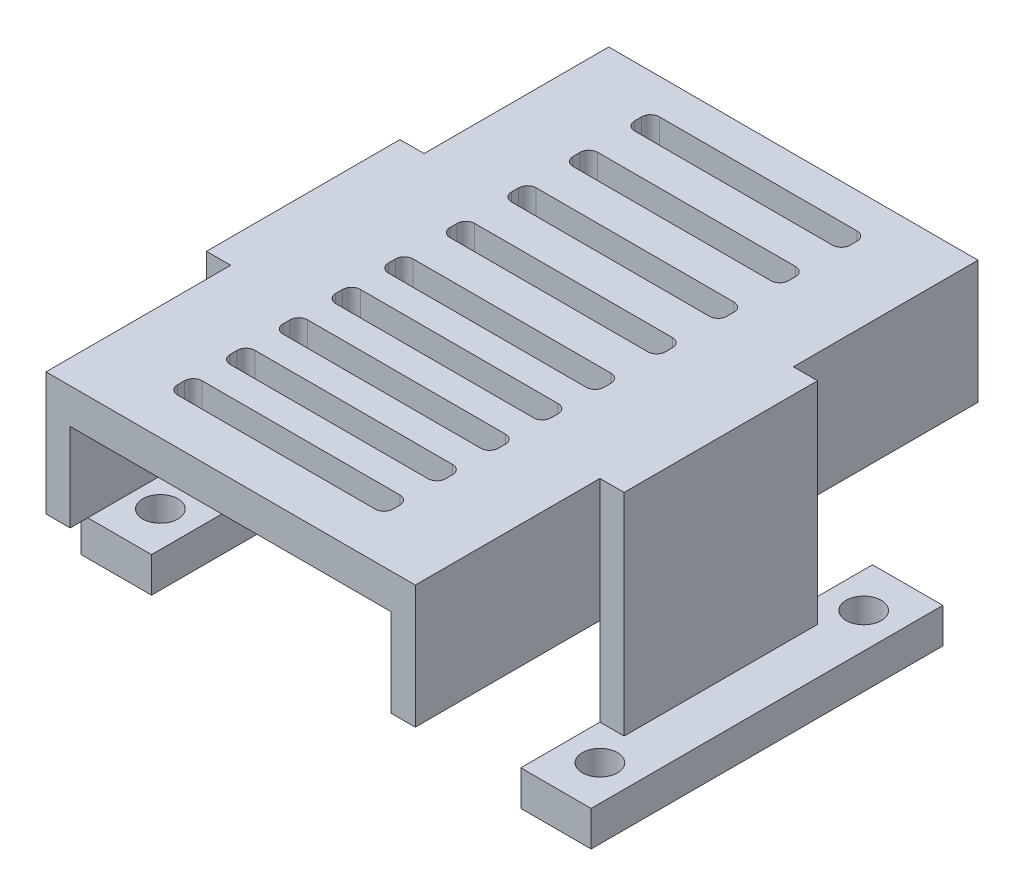
SolidWorks part; units mm, degrees
ref_plane "Front Plane" through (0, 0, 0) normal (0, 0, 1) x (1, 0, 0)
ref_plane "Top Plane" through (0, 0, 0) normal (0, 1, 0) x (1, 0, 0)
ref_plane "Right Plane" through (0, 0, 0) normal (1, 0, 0) x (0, 0, -1)
sketch "Sketch1" plane through (0, 0, 0) normal (0, 0, 1) x (1, 0, 0)
  line L0 (0, -55) -> (0, 55) construction
  line L7 (-23.75, 32) -> (23.75, 32)
  line L8 (-18.25, 28) -> (18.25, 28)
  line L9 (-21.5361, 18) -> (-21, 18) construction
  line L13 (-23.75, 32) -> (-23.75, 8)
  line L17 (21.5361, 18) -> (21, 18) construction
  line L19 (-21, 4) -> (-21, 18)
  line L22 (23.75, 32) -> (23.75, 8)
  line L25 (21, 4) -> (21, 18)
  line L27 (-29, 4) -> (-29, 8)
  line L28 (-29, 8) -> (-23.75, 8)
  line L29 (29, 8) -> (23.75, 8)
  line L30 (29, 4) -> (29, 8)
  line L31 (21, 4) -> (29, 4)
  line L32 (-18.25, 28) -> (-18.25, 18)
  line L33 (-29, 4) -> (-21, 4)
  line L34 (-18.25, 18) -> (-21, 18)
  line L35 (18.25, 28) -> (18.25, 18)
  line L36 (18.25, 18) -> (21, 18)
  dimension "D5" = 8
  dimension "D1" = 10
  dimension "D2" = 4
  dimension "D3" = 14
  dimension "D4" = 2.75
  dimension "D6" = 4
extrude "Boss-Extrude1" add sketch "Sketch1" along normal mid plane 64
sketch "Sketch8" plane through (0, 32, 0) normal (0, 1, 0) x (1, 0, 0)
  line L0 (12.25, 0) -> (-12.25, 0) construction
  line L1 (-12.25, 22.2) -> (12.25, 22.2) construction
  line L2 (-12.25, 22.2) -> (-12.25, -18.3) construction
  line L3 (-12.25, -18.3) -> (12.25, -18.3) construction
  line L4 (12.25, 22.2) -> (12.25, -18.3) construction
  line L5 (12.25, -2.8) -> (-12.25, -2.8) construction
  line L7 (11.25, -2.8) -> (-11.25, -2.8)
  line L8 (12.25, -1.8) -> (12.25, -1)
  line L9 (11.25, 0) -> (-11.25, 0)
  line L10 (-12.25, -1.8) -> (-12.25, -1)
  arc A0 (12.25, -1.8) -> (11.25, -2.8) centre (11.25, -1.8) cw
  arc A1 (12.25, -1) -> (11.25, 0) centre (11.25, -1) ccw
  arc A2 (-12.25, -1.8) -> (-11.25, -2.8) centre (-11.25, -1.8) ccw
  arc A3 (-11.25, 0) -> (-12.25, -1) centre (-11.25, -1) ccw
  dimension "D3" = 1
  dimension "D1" = 40.5
  dimension "D2" = 24.5
  dimension "D4" = 25
  dimension "D5" = 2.8
extrude "Cut-Extrude5" cut sketch "Sketch8" against normal up to surface (4 mm away) contours A2 L10 A3 L9 A1 L8 A0 L7 up to face at (0, 28, 0)
pattern_linear "LPattern1" count 5 spacing 7 along (0, 0, -1) of "Cut-Extrude5"
pattern_linear "LPattern2" count 5 spacing 6 along (0, 0, 1) of "Cut-Extrude5"
sketch "Sketch9" plane through (0, 0, 0) normal (0, 1, 0) x (0, 0, -1)
  line L0 (0, -18.11) -> (0, 18.11) construction
  line L1 (-29.25, 0) -> (29.25, 0) construction
  line L2 (-25, 25) -> (25, 25) construction
  line L3 (-29.25, 18.11) -> (29.25, 18.11) construction
  line L4 (-29.25, 18.11) -> (-29.25, -18.11) construction
  line L5 (-29.25, -18.11) -> (29.25, -18.11) construction
  line L6 (29.25, 18.11) -> (29.25, -18.11) construction
  line L7 (-31, 21) -> (-30, 21)
  line L8 (-32, 20) -> (-32, -20)
  line L9 (-31, -21) -> (-30, -21)
  line L10 (32, 20) -> (32, -20)
  line L11 (-25, -25) -> (25, -25) construction
  line L12 (-29, 25) -> (-29, 22)
  line L13 (-21, 25) -> (-21, 22)
  line L14 (-20, 21) -> (20, 21)
  line L15 (29, 25) -> (29, 22)
  line L16 (21, 25) -> (21, 22)
  line L17 (30, 21) -> (31, 21)
  line L18 (29, -25) -> (29, -22)
  line L19 (21, -25) -> (21, -22)
  line L20 (-21, -25) -> (-21, -22)
  line L21 (-29, -25) -> (-29, -22)
  line L22 (-20, -21) -> (20, -21)
  line L23 (30, -21) -> (31, -21)
  arc A0 (-21, 25) -> (-29, 25) centre (-25, 25) ccw
  arc A1 (-32, 20) -> (-31, 21) centre (-31, 20) cw
  arc A2 (-20, 21) -> (-21, 22) centre (-20, 22) cw
  arc A3 (-29, 22) -> (-30, 21) centre (-30, 22) cw
  arc A4 (29, 22) -> (30, 21) centre (30, 22) ccw
  arc A5 (20, 21) -> (21, 22) centre (20, 22) ccw
  arc A6 (21, 25) -> (29, 25) centre (25, 25) cw
  arc A7 (29, -22) -> (30, -21) centre (30, -22) cw
  arc A8 (21, -25) -> (29, -25) centre (25, -25) ccw
  arc A9 (20, -21) -> (21, -22) centre (20, -22) cw
  arc A10 (-20, -21) -> (-21, -22) centre (-20, -22) ccw
  arc A11 (-21, -25) -> (-29, -25) centre (-25, -25) cw
  arc A12 (-29, -22) -> (-30, -21) centre (-30, -22) ccw
  arc A13 (-31, -21) -> (-32, -20) centre (-31, -20) cw
  arc A14 (32, -20) -> (31, -21) centre (31, -20) cw
  arc A15 (32, 20) -> (31, 21) centre (31, 20) ccw
  point P4 (0, 0)
  point P5 (0, 0)
  point P8 (0, 0)
  point P13 (32, 0)
  point P19 (0, 25)
  point P30 (-21, 21)
  point P62 (-25, 29)
  point P63 (0, 0)
  dimension "D9" = 1
  dimension "D10" = 1
  dimension "D1" = 58.5
  dimension "D2" = 36.22
  dimension "D3" = 64
  dimension "D4" = 42
  dimension "D5" = 2.89
  dimension "D6" = 2.75
  dimension "D7" = 50
  dimension "D8" = 50
  dimension "D11" = 2.75
  dimension "D12" = 42
  dimension "D13" = 8
sketch "Sketch10" plane through (0, 8, 0) normal (0, 1, 0) x (1, 0, 0)
  line L0 (-25, 25) -> (-25, 15) construction
  line L1 (-25, -25) -> (-25, 25) construction
  line L2 (-25, -25) -> (-25, -15) construction
  line L3 (0, -17.6) -> (0, 17.6) construction
  line L4 (25, -25) -> (25, -15) construction
  line L5 (25, 25) -> (25, 15) construction
  dimension "D1" = 10
  dimension "D2" = 10
ref_axis "Axis1" through (-25, 8, 15) along (0, 1, 0)
ref_axis "Axis2" through (-25, 8, -15) along (0, 1, 0)
ref_axis "Axis3" through (25, 8, -15) along (0, 1, 0)
ref_axis "Axis4" through (25, 8, 15) along (0, 1, 0)
ref_plane "Plane1" through (0, 0, -15) normal (0, 0, -1) x (-1, 0, 0)
ref_plane "Plane2" through (0, 0, 15) normal (0, 0, 1) x (1, 0, 0)
ref_plane "Plane3" through (0, 8, 0) normal (0, 1, 0) x (1, 0, 0)
sketch "Sketch11" plane through (0, 0, -15) normal (0, 0, -1) x (-1, 0, 0)
  line L5 (47.7244, 8) -> (-47.7244, 8) construction
  line L6 (21, 39.0594) -> (29, 39.0594)
  line L7 (21, 39.0594) -> (21, 8)
  line L8 (21, 8) -> (29, 8)
  line L9 (29, 39.0594) -> (29, 8)
  line L10 (29, 8) -> (29, 4) construction
  line L11 (0, 17.6) -> (0, -17.6) construction
  line L12 (-29, 39.0594) -> (-29, 8)
  line L13 (-21, 8) -> (-29, 8)
  line L14 (-21, 39.0594) -> (-21, 8)
  line L15 (-21, 39.0594) -> (-29, 39.0594)
  line L16 (-21, 18) -> (-21, 4) construction
  point P18 (18.25, 18)
  dimension "D1" = 0
sketch "Sketch12" plane through (0, 0, -32) normal (0, 0, -1) x (-1, 0, 0)
  line L10 (-29, 8) -> (-23.75, 8) construction
  line L11 (29, 8) -> (21, 8)
  line L12 (29, 8) -> (29, 4)
  line L13 (29, 4) -> (21, 4)
  line L14 (21, 8) -> (21, 4)
  line L15 (-29, 8) -> (-21, 8)
  line L16 (-29, 8) -> (-29, 4)
  line L17 (-29, 4) -> (-21, 4)
  line L18 (-21, 8) -> (-21, 4)
  line L19 (-29, 4) -> (-29, 8) construction
extrude "Cut-Extrude7" cut sketch "Sketch12" against normal up to vertex (12 mm away) up to point (-21, 0, -20)
mirror "Mirror1" about plane through (0, 0, 0) normal (0, 0, 1) of "Cut-Extrude7"
extrude "Cut-Extrude8" cut sketch "Sketch11" along normal up to surface (17 mm away) and the other way blind 4 up to face at (0, 18.6667, -32)
sketch "Sketch13" plane through (0, 0, 15) normal (0, 0, 1) x (1, 0, 0)
  line L0 (-21, 8) -> (-21, 18) construction
  line L6 (21, 36.8693) -> (31.75, 36.8693)
  line L7 (21, 36.8693) -> (21, 8)
  line L8 (21, 8) -> (31.75, 8)
  line L9 (31.75, 36.8693) -> (31.75, 8)
  line L12 (-28.0569, 37.9363) -> (-28.0569, 8)
  line L13 (-21, 8) -> (-28.0569, 8)
  line L14 (-21, 37.9363) -> (-21, 8)
  line L15 (-21, 37.9363) -> (-28.0569, 37.9363)
  line L16 (21, 18) -> (21, 8) construction
  dimension "D1" = 0
  dimension "D2" = 0
extrude "Cut-Extrude10" cut sketch "Sketch13" along normal up to surface (17 mm away) and the other way blind 4 up to face at (0, 18.6667, 32)
hole_wizard "Ø4.0mm Dowel Hole1" positions "Sketch14" profile "Sketch15" hole size "Ø4.0" standard "ANSI Metric" end condition through all
sketch "Sketch14" plane through (0, 8, 0) normal (0, 1, 0) x (1, 0, 0)
  point P0 (25, -15)
  point P3 (25, 15)
  point P6 (-25, 15)
  point P9 (-25, -15)
sketch "Sketch15" plane through (25, 8, 15) normal (1, 0, 0) x (0, 0, 1)
  line L0 (0, 0) -> (0, 4)
  line L1 (0, 4) -> (2, 4)
  line L2 (2, 4) -> (2, 0)
  line L5 (2, 0) -> (0, 0)
  line L11 (0, -6.35) -> (0, 107.95) construction
  dimension "Thru Hole Dia." = 4
  dimension "Thru Hole Depth" = 4
